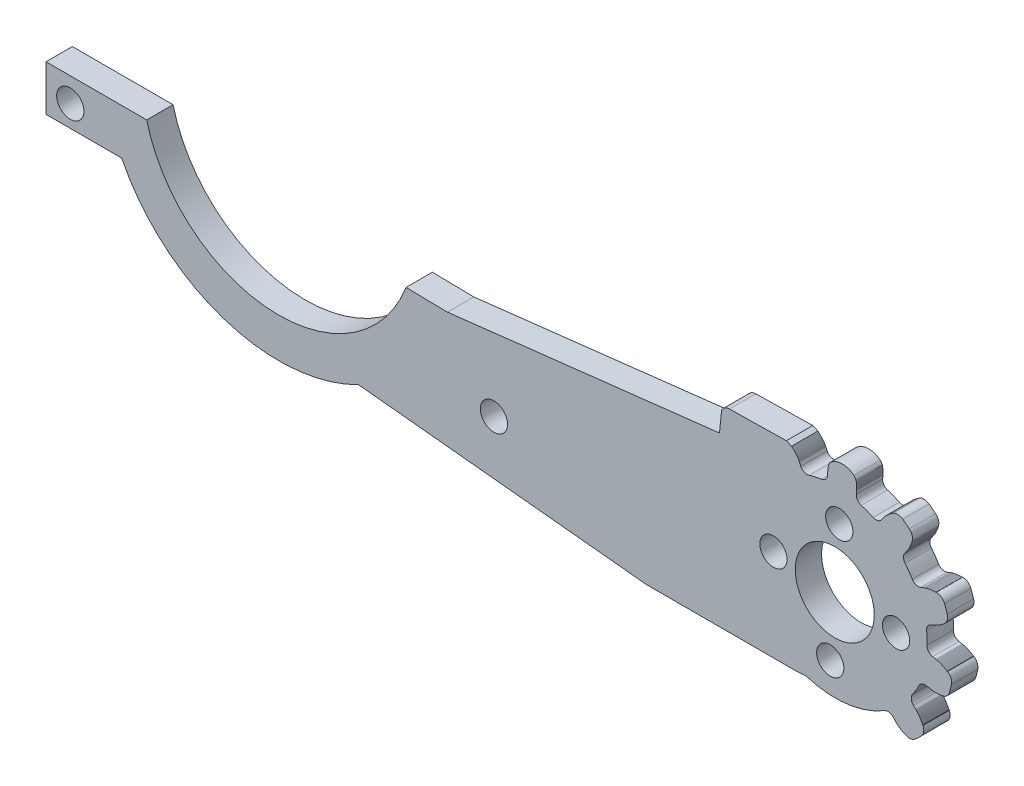
SolidWorks part; units mm, degrees
ref_plane "前视基准面" through (0, 0, 0) normal (0, 0, 1) x (1, 0, 0)
ref_plane "上视基准面" through (0, 0, 0) normal (0, 1, 0) x (1, 0, 0)
ref_plane "右视基准面" through (0, 0, 0) normal (1, 0, 0) x (0, 0, -1)
sketch "Model" plane through (0, 0, 0) normal (0, 0, 1) x (1, 0, 0)
  line L0 (3139.6381, 1742.7841) -> (3139.6125, 1742.8095)
  line L1 (3139.6635, 1742.7586) -> (3139.6381, 1742.7841)
  line L2 (3139.8365, 1742.5753) -> (3139.8124, 1742.602)
  line L3 (3153.0408, 1740.3213) -> (3153.0525, 1740.3554)
  line L4 (3153.0289, 1740.2873) -> (3153.0408, 1740.3213)
  line L5 (3153.0169, 1740.2533) -> (3153.0289, 1740.2873)
  line L6 (3153.0046, 1740.2194) -> (3153.0169, 1740.2533)
  line L7 (3152.9921, 1740.1856) -> (3153.0046, 1740.2194)
  line L8 (3152.9795, 1740.1519) -> (3152.9921, 1740.1856)
  line L9 (3152.87, 1739.8856) -> (3152.8846, 1739.9185)
  line L10 (3152.8242, 1739.788) -> (3152.8398, 1739.8203)
  line L11 (3154.7478, 1736.7119) -> (3154.7132, 1736.7018)
  line L12 (3154.7825, 1736.7216) -> (3154.7478, 1736.7119)
  line L13 (3154.8172, 1736.7308) -> (3154.7825, 1736.7216)
  line L14 (3154.8521, 1736.7395) -> (3154.8172, 1736.7308)
  line L15 (3154.8871, 1736.7479) -> (3154.8521, 1736.7395)
  line L16 (3154.9222, 1736.7557) -> (3154.8871, 1736.7479)
  line L17 (3154.9574, 1736.7631) -> (3154.9222, 1736.7557)
  line L18 (3154.9926, 1736.77) -> (3154.9574, 1736.7631)
  line L19 (3155.028, 1736.7765) -> (3154.9926, 1736.77)
  line L20 (3155.0634, 1736.7826) -> (3155.028, 1736.7765)
  line L21 (3155.1344, 1736.7936) -> (3155.0989, 1736.7883)
  line L22 (3155.17, 1736.7985) -> (3155.1344, 1736.7936)
  line L23 (3156.468, 1733.9968) -> (3156.497, 1734.0182)
  line L24 (3156.4389, 1733.9757) -> (3156.468, 1733.9968)
  line L25 (3156.4096, 1733.9547) -> (3156.4389, 1733.9757)
  line L26 (3156.3802, 1733.9339) -> (3156.4096, 1733.9547)
  line L27 (3156.3506, 1733.9134) -> (3156.3802, 1733.9339)
  line L28 (3156.3209, 1733.8931) -> (3156.3506, 1733.9134)
  line L29 (3156.291, 1733.8731) -> (3156.3209, 1733.8931)
  line L30 (3156.2609, 1733.8533) -> (3156.291, 1733.8731)
  line L31 (3156.2307, 1733.8339) -> (3156.2609, 1733.8533)
  line L32 (3156.2003, 1733.8148) -> (3156.2307, 1733.8339)
  line L33 (3156.1696, 1733.796) -> (3156.2003, 1733.8148)
  line L34 (3156.4614, 1730.0427) -> (3156.4285, 1730.0571)
  line L35 (3156.4942, 1730.028) -> (3156.4614, 1730.0427)
  line L36 (3156.5269, 1730.0129) -> (3156.4942, 1730.028)
  line L37 (3155.2801, 1726.9965) -> (3155.3155, 1726.99)
  line L38 (3155.2448, 1727.0034) -> (3155.2801, 1726.9965)
  line L39 (3155.1394, 1727.0265) -> (3155.1744, 1727.0185)
  line L40 (3155.1044, 1727.035) -> (3155.1394, 1727.0265)
  line L41 (3154.7261, 1727.0734) -> (3155.1044, 1727.035)
  line L42 (3139.9527, 1742.4382) -> (3139.9301, 1742.4661)
  line L43 (3139.9751, 1742.4101) -> (3139.9527, 1742.4382)
  line L44 (3152.9666, 1740.1183) -> (3152.9795, 1740.1519)
  line L45 (3152.9267, 1740.0179) -> (3152.9402, 1740.0512)
  line L46 (3152.8989, 1739.9515) -> (3152.9129, 1739.9846)
  line L47 (3152.8846, 1739.9185) -> (3152.8989, 1739.9515)
  line L48 (3155.3488, 1736.8185) -> (3155.313, 1736.8151)
  line L49 (3152.8551, 1739.8529) -> (3152.87, 1739.8856)
  line L50 (3152.8398, 1739.8203) -> (3152.8551, 1739.8529)
  line L51 (3152.8082, 1739.7558) -> (3152.8242, 1739.788)
  line L52 (3152.7919, 1739.7238) -> (3152.8082, 1739.7558)
  line L53 (3155.2095, 1727.0108) -> (3155.2448, 1727.0034)
  line L54 (3155.951, 1730.2151) -> (3155.916, 1730.2232)
  line L55 (3139.8603, 1742.5483) -> (3139.8365, 1742.5753)
  line L56 (3139.8838, 1742.5212) -> (3139.8603, 1742.5483)
  line L57 (3139.9071, 1742.4938) -> (3139.8838, 1742.5212)
  line L58 (3139.9301, 1742.4661) -> (3139.9071, 1742.4938)
  line L59 (3139.997, 1742.3817) -> (3139.9751, 1742.4101)
  line L60 (3152.9535, 1740.0847) -> (3152.9666, 1740.1183)
  line L61 (3152.9402, 1740.0512) -> (3152.9535, 1740.0847)
  line L62 (3140.0607, 1742.2947) -> (3140.0399, 1742.324)
  line L63 (3155.2057, 1736.8031) -> (3155.17, 1736.7985)
  line L64 (3152.9129, 1739.9846) -> (3152.9267, 1740.0179)
  line L65 (3156.497, 1734.0182) -> (3156.5259, 1734.0397)
  line L66 (3154.179, 1723.2587) -> (3154.162, 1723.2905)
  line L67 (3154.1959, 1723.2269) -> (3154.179, 1723.2587)
  line L68 (3154.2125, 1723.1949) -> (3154.1959, 1723.2269)
  line L69 (3154.2289, 1723.1628) -> (3154.2125, 1723.1949)
  line L70 (3154.2452, 1723.1307) -> (3154.2289, 1723.1628)
  line L71 (3154.2612, 1723.0984) -> (3154.2452, 1723.1307)
  line L72 (3154.277, 1723.066) -> (3154.2612, 1723.0984)
  line L73 (3154.2927, 1723.0336) -> (3154.277, 1723.066)
  line L74 (3154.3081, 1723.001) -> (3154.2927, 1723.0336)
  line L75 (3154.3338, 1722.9732) -> (3154.3081, 1723.001)
  line L76 (3152.3422, 1721.044) -> (3152.3796, 1721.0389)
  line L77 (3152.3097, 1721.0596) -> (3152.3422, 1721.044)
  line L78 (3152.2773, 1721.0754) -> (3152.3097, 1721.0596)
  line L79 (3155.0989, 1736.7883) -> (3155.0634, 1736.7826)
  line L80 (3140.0399, 1742.324) -> (3140.0186, 1742.353)
  line L81 (3156.0903, 1730.1784) -> (3156.0556, 1730.1882)
  line L82 (3156.1248, 1730.1682) -> (3156.0903, 1730.1784)
  line L83 (3152.2451, 1721.0914) -> (3152.2773, 1721.0754)
  line L84 (3152.2129, 1721.1075) -> (3152.2451, 1721.0914)
  line L85 (3156.4285, 1730.0571) -> (3156.3954, 1730.0711)
  line L86 (3146.7836, 1742.877) -> (3146.781, 1742.9128)
  line L87 (3146.7858, 1742.8411) -> (3146.7836, 1742.877)
  line L88 (3146.7875, 1742.8052) -> (3146.7858, 1742.8411)
  line L89 (3146.7888, 1742.7692) -> (3146.7875, 1742.8052)
  line L90 (3146.7896, 1742.7333) -> (3146.7888, 1742.7692)
  line L91 (3146.7899, 1742.6973) -> (3146.7896, 1742.7333)
  line L92 (3146.7898, 1742.6613) -> (3146.7899, 1742.6973)
  line L93 (3146.7893, 1742.6253) -> (3146.7898, 1742.6613)
  line L94 (3146.7883, 1742.5893) -> (3146.7893, 1742.6253)
  line L95 (3146.7869, 1742.5533) -> (3146.7883, 1742.5893)
  line L96 (3146.7851, 1742.5174) -> (3146.7869, 1742.5533)
  line L97 (3146.7828, 1742.4815) -> (3146.7851, 1742.5174)
  line L98 (3146.7802, 1742.4456) -> (3146.7828, 1742.4815)
  line L99 (3146.7772, 1742.4097) -> (3146.7802, 1742.4456)
  line L100 (3146.7738, 1742.374) -> (3146.7772, 1742.4097)
  line L101 (3146.7513, 1741.9979) -> (3146.7738, 1742.374)
  line L102 (3149.8509, 1741.2183) -> (3149.6326, 1740.9116)
  line L103 (3140.0186, 1742.353) -> (3139.997, 1742.3817)
  line L104 (3149.8719, 1741.2475) -> (3149.8509, 1741.2183)
  line L105 (3149.8932, 1741.2765) -> (3149.8719, 1741.2475)
  line L106 (3149.9149, 1741.3052) -> (3149.8932, 1741.2765)
  line L107 (3155.2414, 1736.8074) -> (3155.2057, 1736.8031)
  line L108 (3155.2772, 1736.8114) -> (3155.2414, 1736.8074)
  line L109 (3155.313, 1736.8151) -> (3155.2772, 1736.8114)
  line L110 (3156.4629, 1726.9866) -> (3156.4986, 1726.9911)
  line L111 (3156.4271, 1726.9824) -> (3156.4629, 1726.9866)
  line L112 (3155.986, 1730.2065) -> (3155.951, 1730.2151)
  line L113 (3156.0209, 1730.1976) -> (3155.986, 1730.2065)
  line L114 (3156.0556, 1730.1882) -> (3156.0209, 1730.1976)
  line L115 (3156.1592, 1730.1576) -> (3156.1248, 1730.1682)
  line L116 (3156.7523, 1734.2181) -> (3156.7799, 1734.2412)
  line L117 (3156.7245, 1734.1952) -> (3156.7523, 1734.2181)
  line L118 (3156.6965, 1734.1725) -> (3156.7245, 1734.1952)
  line L119 (3156.6684, 1734.1499) -> (3156.6965, 1734.1725)
  line L120 (3156.6402, 1734.1275) -> (3156.6684, 1734.1499)
  line L121 (3156.6118, 1734.1053) -> (3156.6402, 1734.1275)
  line L122 (3156.5833, 1734.0833) -> (3156.6118, 1734.1053)
  line L123 (3156.5547, 1734.0614) -> (3156.5833, 1734.0833)
  line L124 (3156.5259, 1734.0397) -> (3156.5547, 1734.0614)
  line L125 (3153.0639, 1740.3896) -> (3153.0751, 1740.4238)
  line L126 (3153.0525, 1740.3554) -> (3153.0639, 1740.3896)
  line L127 (3155.2459, 1733.3476) -> (3155.5833, 1733.5244)
  line L128 (3156.1934, 1730.1466) -> (3156.1592, 1730.1576)
  line L129 (3156.2275, 1730.1351) -> (3156.1934, 1730.1466)
  line L130 (3156.2615, 1730.1232) -> (3156.2275, 1730.1351)
  line L131 (3156.2952, 1730.1108) -> (3156.2615, 1730.1232)
  line L132 (3156.3288, 1730.098) -> (3156.2952, 1730.1108)
  line L133 (3156.3622, 1730.0848) -> (3156.3288, 1730.098)
  line L134 (3156.3954, 1730.0711) -> (3156.3622, 1730.0848)
  line L135 (3143.5454, 1743.0444) -> (3143.5389, 1743.0091)
  line L136 (3143.5524, 1743.0797) -> (3143.5454, 1743.0444)
  line L137 (3143.5598, 1743.1149) -> (3143.5524, 1743.0797)
  line L138 (3143.5677, 1743.15) -> (3143.5598, 1743.1149)
  line L139 (3143.5761, 1743.1849) -> (3143.5677, 1743.15)
  line L140 (3143.5848, 1743.2197) -> (3143.5761, 1743.1849)
  line L141 (3143.594, 1743.2545) -> (3143.5848, 1743.2197)
  line L142 (3143.6036, 1743.2891) -> (3143.594, 1743.2545)
  line L143 (3143.6135, 1743.3237) -> (3143.6036, 1743.2891)
  line L144 (3143.6345, 1743.3925) -> (3143.6238, 1743.3581)
  line L145 (3143.6454, 1743.4267) -> (3143.6345, 1743.3925)
  line L146 (3143.6567, 1743.4609) -> (3143.6454, 1743.4267)
  line L147 (3143.6682, 1743.495) -> (3143.6567, 1743.4609)
  line L148 (3143.68, 1743.5291) -> (3143.6682, 1743.495)
  line L149 (3143.686, 1743.546) -> (3143.68, 1743.5291)
  line L150 (3156.1388, 1733.7775) -> (3156.1696, 1733.796)
  line L151 (3156.1077, 1733.7594) -> (3156.1388, 1733.7775)
  line L152 (3155.5833, 1733.5244) -> (3155.6173, 1733.5362)
  line L153 (3155.8104, 1730.2453) -> (3155.4407, 1730.3164)
  line L154 (3155.8457, 1730.2383) -> (3155.8104, 1730.2453)
  line L155 (3155.8809, 1730.231) -> (3155.8457, 1730.2383)
  line L156 (3155.916, 1730.2232) -> (3155.8809, 1730.231)
  line L157 (3146.7256, 1743.3043) -> (3146.7187, 1743.3396)
  line L158 (3146.7323, 1743.2689) -> (3146.7256, 1743.3043)
  line L159 (3146.7387, 1743.2335) -> (3146.7323, 1743.2689)
  line L160 (3146.7448, 1743.198) -> (3146.7387, 1743.2335)
  line L161 (3146.7506, 1743.1625) -> (3146.7448, 1743.198)
  line L162 (3146.7561, 1743.127) -> (3146.7506, 1743.1625)
  line L163 (3146.7612, 1743.0914) -> (3146.7561, 1743.127)
  line L164 (3146.7659, 1743.0557) -> (3146.7612, 1743.0914)
  line L165 (3146.7703, 1743.0201) -> (3146.7659, 1743.0557)
  line L166 (3146.7743, 1742.9844) -> (3146.7703, 1743.0201)
  line L167 (3146.7779, 1742.9486) -> (3146.7743, 1742.9844)
  line L168 (3146.781, 1742.9128) -> (3146.7779, 1742.9486)
  line L169 (3153.0969, 1740.4925) -> (3153.0997, 1740.5293)
  line L170 (3156.0765, 1733.7417) -> (3156.1077, 1733.7594)
  line L171 (3155.7852, 1733.6007) -> (3155.8184, 1733.6147)
  line L172 (3155.7519, 1733.587) -> (3155.7852, 1733.6007)
  line L173 (3155.7185, 1733.5737) -> (3155.7519, 1733.587)
  line L174 (3155.6849, 1733.5608) -> (3155.7185, 1733.5737)
  line L175 (3155.6512, 1733.5483) -> (3155.6849, 1733.5608)
  line L176 (3155.6173, 1733.5362) -> (3155.6512, 1733.5483)
  line L177 (3151.8657, 1721.2984) -> (3151.8967, 1721.28)
  line L178 (3152.7752, 1739.692) -> (3152.7919, 1739.7238)
  line L179 (3152.7225, 1739.5979) -> (3152.7405, 1739.629)
  line L180 (3139.5087, 1742.9095) -> (3139.4824, 1742.9341)
  line L181 (3139.5349, 1742.8847) -> (3139.5087, 1742.9095)
  line L182 (3139.5609, 1742.8598) -> (3139.5349, 1742.8847)
  line L183 (3139.5868, 1742.8347) -> (3139.5609, 1742.8598)
  line L184 (3139.6125, 1742.8095) -> (3139.5868, 1742.8347)
  line L185 (3154.5424, 1736.6452) -> (3154.5087, 1736.6328)
  line L186 (3139.6888, 1742.7329) -> (3139.6635, 1742.7586)
  line L187 (3139.7139, 1742.707) -> (3139.6888, 1742.7329)
  line L188 (3139.7388, 1742.6811) -> (3139.7139, 1742.707)
  line L189 (3139.7635, 1742.6549) -> (3139.7388, 1742.6811)
  line L190 (3139.7881, 1742.6285) -> (3139.7635, 1742.6549)
  line L191 (3139.8124, 1742.602) -> (3139.7881, 1742.6285)
  line L192 (3140.0812, 1742.2651) -> (3140.0607, 1742.2947)
  line L193 (3140.1013, 1742.2353) -> (3140.0812, 1742.2651)
  line L194 (3140.1211, 1742.2052) -> (3140.1013, 1742.2353)
  line L195 (3140.1404, 1742.1748) -> (3140.1211, 1742.2052)
  line L196 (3140.1594, 1742.1443) -> (3140.1404, 1742.1748)
  line L197 (3140.1781, 1742.1135) -> (3140.1594, 1742.1443)
  line L198 (3140.1963, 1742.0824) -> (3140.1781, 1742.1135)
  line L199 (3140.2143, 1742.0512) -> (3140.1963, 1742.0824)
  line L200 (3140.2318, 1742.0198) -> (3140.2143, 1742.0512)
  line L201 (3140.249, 1741.9882) -> (3140.2318, 1742.0198)
  line L202 (3140.2658, 1741.9564) -> (3140.249, 1741.9882)
  line L203 (3140.2823, 1741.9245) -> (3140.2658, 1741.9564)
  line L204 (3140.4359, 1741.5802) -> (3140.2823, 1741.9245)
  line L205 (3143.4957, 1742.6159) -> (3143.4779, 1742.2399)
  line L206 (3143.4976, 1742.6518) -> (3143.4957, 1742.6159)
  line L207 (3143.4999, 1742.6877) -> (3143.4976, 1742.6518)
  line L208 (3143.5026, 1742.7235) -> (3143.4999, 1742.6877)
  line L209 (3143.5056, 1742.7594) -> (3143.5026, 1742.7235)
  line L210 (3143.5091, 1742.7952) -> (3143.5056, 1742.7594)
  line L211 (3143.513, 1742.831) -> (3143.5091, 1742.7952)
  line L212 (3143.5173, 1742.8668) -> (3143.513, 1742.831)
  line L213 (3143.5221, 1742.9024) -> (3143.5173, 1742.8668)
  line L214 (3143.5272, 1742.9381) -> (3143.5221, 1742.9024)
  line L215 (3143.5329, 1742.9736) -> (3143.5272, 1742.9381)
  line L216 (3143.5389, 1743.0091) -> (3143.5329, 1742.9736)
  line L217 (3154.0741, 1723.4476) -> (3154.0559, 1723.4787)
  line L218 (3154.0921, 1723.4164) -> (3154.0741, 1723.4476)
  line L219 (3154.1099, 1723.3851) -> (3154.0921, 1723.4164)
  line L220 (3154.1274, 1723.3537) -> (3154.1099, 1723.3851)
  line L221 (3154.1448, 1723.3221) -> (3154.1274, 1723.3537)
  line L222 (3154.162, 1723.2905) -> (3154.1448, 1723.3221)
  line L223 (3150.8201, 1742.1198) -> (3150.7904, 1742.0996)
  line L224 (3150.85, 1742.1399) -> (3150.8201, 1742.1198)
  line L225 (3150.8801, 1742.1598) -> (3150.85, 1742.1399)
  line L226 (3150.9061, 1742.1859) -> (3150.8801, 1742.1598)
  line L227 (3153.0861, 1740.4581) -> (3153.0969, 1740.4925)
  line L228 (3153.0751, 1740.4238) -> (3153.0861, 1740.4581)
  line L229 (3156.045, 1733.7244) -> (3156.0765, 1733.7417)
  line L230 (3156.0133, 1733.7075) -> (3156.045, 1733.7244)
  line L231 (3155.9491, 1733.675) -> (3155.9813, 1733.691)
  line L232 (3155.9167, 1733.6593) -> (3155.9491, 1733.675)
  line L233 (3155.8841, 1733.644) -> (3155.9167, 1733.6593)
  line L234 (3155.8513, 1733.6292) -> (3155.8841, 1733.644)
  line L235 (3155.8184, 1733.6147) -> (3155.8513, 1733.6292)
  line L236 (3152.0851, 1721.1742) -> (3152.1169, 1721.1573)
  line L237 (3152.0534, 1721.1914) -> (3152.0851, 1721.1742)
  line L238 (3152.0218, 1721.2087) -> (3152.0534, 1721.1914)
  line L239 (3151.9904, 1721.2263) -> (3152.0218, 1721.2087)
  line L240 (3151.959, 1721.244) -> (3151.9904, 1721.2263)
  line L241 (3151.9278, 1721.2619) -> (3151.959, 1721.244)
  line L242 (3151.8967, 1721.28) -> (3151.9278, 1721.2619)
  line L243 (3150.0998, 1741.5257) -> (3150.0755, 1741.4992)
  line L244 (3151.7135, 1721.3942) -> (3151.7436, 1721.3744)
  line L245 (3151.6837, 1721.4142) -> (3151.7135, 1721.3942)
  line L246 (3151.6247, 1721.4553) -> (3151.6541, 1721.4346)
  line L247 (3151.5956, 1721.4764) -> (3151.6247, 1721.4553)
  line L248 (3151.5668, 1721.4979) -> (3151.5956, 1721.4764)
  line L249 (3151.5383, 1721.5197) -> (3151.5668, 1721.4979)
  line L250 (3151.51, 1721.5419) -> (3151.5383, 1721.5197)
  line L251 (3151.482, 1721.5645) -> (3151.51, 1721.5419)
  line L252 (3151.4543, 1721.5875) -> (3151.482, 1721.5645)
  line L253 (3151.4269, 1721.6108) -> (3151.4543, 1721.5875)
  line L254 (3151.3998, 1721.6345) -> (3151.4269, 1721.6108)
  line L255 (3151.3729, 1721.6584) -> (3151.3998, 1721.6345)
  line L256 (3151.3464, 1721.6827) -> (3151.3729, 1721.6584)
  line L257 (3151.3201, 1721.7074) -> (3151.3464, 1721.6827)
  line L258 (3151.2941, 1721.7323) -> (3151.3201, 1721.7074)
  line L259 (3151.2684, 1721.7575) -> (3151.2941, 1721.7323)
  line L260 (3151.243, 1721.783) -> (3151.2684, 1721.7575)
  line L261 (3151.2179, 1721.8087) -> (3151.243, 1721.783)
  line L262 (3151.1931, 1721.8347) -> (3151.2179, 1721.8087)
  line L263 (3150.9347, 1722.1084) -> (3151.1931, 1721.8347)
  line L264 (3155.1744, 1727.0185) -> (3155.2095, 1727.0108)
  line L265 (3156.8465, 1729.8473) -> (3156.815, 1729.8648)
  line L266 (3156.8779, 1729.8296) -> (3156.8465, 1729.8473)
  line L267 (3149.9368, 1741.3337) -> (3149.9149, 1741.3052)
  line L268 (3149.9591, 1741.3619) -> (3149.9368, 1741.3337)
  line L269 (3149.9818, 1741.3899) -> (3149.9591, 1741.3619)
  line L270 (3150.0047, 1741.4177) -> (3149.9818, 1741.3899)
  line L271 (3150.028, 1741.4451) -> (3150.0047, 1741.4177)
  line L272 (3150.0516, 1741.4723) -> (3150.028, 1741.4451)
  line L273 (3150.0755, 1741.4992) -> (3150.0516, 1741.4723)
  line L274 (3155.4565, 1736.8273) -> (3155.4206, 1736.8246)
  line L275 (3150.1244, 1741.552) -> (3150.0998, 1741.5257)
  line L276 (3150.1493, 1741.5779) -> (3150.1244, 1741.552)
  line L277 (3150.1746, 1741.6034) -> (3150.1493, 1741.5779)
  line L278 (3150.2002, 1741.6287) -> (3150.1746, 1741.6034)
  line L279 (3150.2261, 1741.6536) -> (3150.2002, 1741.6287)
  line L280 (3150.2523, 1741.6781) -> (3150.2261, 1741.6536)
  line L281 (3150.2788, 1741.7024) -> (3150.2523, 1741.6781)
  line L282 (3150.3056, 1741.7264) -> (3150.2788, 1741.7024)
  line L283 (3150.3327, 1741.7501) -> (3150.3056, 1741.7264)
  line L284 (3150.36, 1741.7735) -> (3150.3327, 1741.7501)
  line L285 (3150.3875, 1741.7966) -> (3150.36, 1741.7735)
  line L286 (3150.4152, 1741.8195) -> (3150.3875, 1741.7966)
  line L287 (3150.4432, 1741.8422) -> (3150.4152, 1741.8195)
  line L288 (3150.4713, 1741.8647) -> (3150.4432, 1741.8422)
  line L289 (3150.4996, 1741.8869) -> (3150.4713, 1741.8647)
  line L290 (3150.5281, 1741.909) -> (3150.4996, 1741.8869)
  line L291 (3150.5567, 1741.9308) -> (3150.5281, 1741.909)
  line L292 (3150.5854, 1741.9525) -> (3150.5567, 1741.9308)
  line L293 (3150.6143, 1741.9741) -> (3150.5854, 1741.9525)
  line L294 (3150.6433, 1741.9954) -> (3150.6143, 1741.9741)
  line L295 (3150.6725, 1742.0166) -> (3150.6433, 1741.9954)
  line L296 (3150.7018, 1742.0376) -> (3150.6725, 1742.0166)
  line L297 (3150.7312, 1742.0584) -> (3150.7018, 1742.0376)
  line L298 (3150.7607, 1742.0791) -> (3150.7312, 1742.0584)
  line L299 (3150.7904, 1742.0996) -> (3150.7607, 1742.0791)
  line L300 (3155.3865, 1726.9783) -> (3155.4221, 1726.973)
  line L301 (3155.351, 1726.9839) -> (3155.3865, 1726.9783)
  line L302 (3155.3155, 1726.99) -> (3155.351, 1726.9839)
  line L303 (3154.6103, 1736.6691) -> (3154.5763, 1736.6573)
  line L304 (3154.6445, 1736.6804) -> (3154.6103, 1736.6691)
  line L305 (3154.6788, 1736.6913) -> (3154.6445, 1736.6804)
  line L306 (3154.7132, 1736.7018) -> (3154.6788, 1736.6913)
  line L307 (3156.7517, 1729.8993) -> (3156.7199, 1729.9162)
  line L308 (3156.7834, 1729.8821) -> (3156.7517, 1729.8993)
  line L309 (3156.815, 1729.8648) -> (3156.7834, 1729.8821)
  line L310 (3152.6853, 1739.5363) -> (3152.7041, 1739.5669)
  line L311 (3152.6662, 1739.5058) -> (3152.6853, 1739.5363)
  line L312 (3156.9091, 1729.8117) -> (3156.8779, 1729.8296)
  line L313 (3156.9403, 1729.7936) -> (3156.9091, 1729.8117)
  line L314 (3156.9713, 1729.7753) -> (3156.9403, 1729.7936)
  line L315 (3155.9813, 1733.691) -> (3156.0133, 1733.7075)
  line L316 (3157.0331, 1729.7381) -> (3157.0023, 1729.7568)
  line L317 (3157.0638, 1729.7193) -> (3157.0331, 1729.7381)
  line L318 (3152.1808, 1721.1239) -> (3152.2129, 1721.1075)
  line L319 (3152.1488, 1721.1405) -> (3152.1808, 1721.1239)
  line L320 (3152.1169, 1721.1573) -> (3152.1488, 1721.1405)
  line L321 (3153.5226, 1724.1537) -> (3153.2501, 1724.4134)
  line L322 (3153.5485, 1724.1288) -> (3153.5226, 1724.1537)
  line L323 (3155.3847, 1736.8216) -> (3155.3488, 1736.8185)
  line L324 (3155.4206, 1736.8246) -> (3155.3847, 1736.8216)
  line L325 (3156.3913, 1726.9784) -> (3156.4271, 1726.9824)
  line L326 (3155.4925, 1736.8298) -> (3155.4565, 1736.8273)
  line L327 (3151.8349, 1721.317) -> (3151.8657, 1721.2984)
  line L328 (3151.8043, 1721.3359) -> (3151.8349, 1721.317)
  line L329 (3152.758, 1739.6604) -> (3152.7752, 1739.692)
  line L330 (3152.7405, 1739.629) -> (3152.758, 1739.6604)
  line L331 (3155.7084, 1736.8402) -> (3155.6724, 1736.839)
  line L332 (3152.7041, 1739.5669) -> (3152.7225, 1739.5979)
  line L333 (3155.7444, 1736.8411) -> (3155.7084, 1736.8402)
  line L334 (3155.7804, 1736.8419) -> (3155.7444, 1736.8411)
  line L335 (3152.6466, 1739.4756) -> (3152.6662, 1739.5058)
  line L336 (3152.6267, 1739.4456) -> (3152.6466, 1739.4756)
  line L337 (3152.6064, 1739.4159) -> (3152.6267, 1739.4456)
  line L338 (3152.5858, 1739.3864) -> (3152.6064, 1739.4159)
  line L339 (3152.5648, 1739.3571) -> (3152.5858, 1739.3864)
  line L340 (3152.5435, 1739.3281) -> (3152.5648, 1739.3571)
  line L341 (3152.5219, 1739.2993) -> (3152.5435, 1739.3281)
  line L342 (3152.5, 1739.2708) -> (3152.5219, 1739.2993)
  line L343 (3152.4778, 1739.2425) -> (3152.5, 1739.2708)
  line L344 (3152.2785, 1738.9201) -> (3152.4778, 1739.2425)
  line L345 (3154.4416, 1736.6067) -> (3154.0922, 1736.4667)
  line L346 (3154.4751, 1736.6199) -> (3154.4416, 1736.6067)
  line L347 (3154.5087, 1736.6328) -> (3154.4751, 1736.6199)
  line L348 (3156.5593, 1729.9974) -> (3156.5269, 1730.0129)
  line L349 (3154.5763, 1736.6573) -> (3154.5424, 1736.6452)
  line L350 (3156.5917, 1729.9817) -> (3156.5593, 1729.9974)
  line L351 (3156.6239, 1729.9657) -> (3156.5917, 1729.9817)
  line L352 (3156.6561, 1729.9495) -> (3156.6239, 1729.9657)
  line L353 (3156.6881, 1729.933) -> (3156.6561, 1729.9495)
  line L354 (3156.7199, 1729.9162) -> (3156.6881, 1729.933)
  line L355 (3156.14, 1726.9564) -> (3156.176, 1726.9589)
  line L356 (3153.7455, 1723.9189) -> (3153.7219, 1723.9461)
  line L357 (3156.1041, 1726.9542) -> (3156.14, 1726.9564)
  line L358 (3155.8165, 1736.8424) -> (3155.7804, 1736.8419)
  line L359 (3155.8524, 1736.8561) -> (3155.8165, 1736.8424)
  line L360 (3153.9206, 1723.6909) -> (3153.9, 1723.7203)
  line L361 (3157.0023, 1729.7568) -> (3156.9713, 1729.7753)
  line L362 (3156.7799, 1734.2412) -> (3156.7986, 1734.2749)
  line L363 (3157.0944, 1729.7002) -> (3157.0638, 1729.7193)
  line L364 (3157.1328, 1729.6935) -> (3157.0944, 1729.7002)
  line L365 (3156.4986, 1726.9911) -> (3156.5323, 1727.0105)
  line L366 (3153.5741, 1724.1035) -> (3153.5485, 1724.1288)
  line L367 (3156.3554, 1726.9746) -> (3156.3913, 1726.9784)
  line L368 (3155.5284, 1736.8321) -> (3155.4925, 1736.8298)
  line L369 (3155.5644, 1736.8341) -> (3155.5284, 1736.8321)
  line L370 (3155.6004, 1736.836) -> (3155.5644, 1736.8341)
  line L371 (3155.6364, 1736.8376) -> (3155.6004, 1736.836)
  line L372 (3155.6724, 1736.839) -> (3155.6364, 1736.8376)
  line L373 (3151.7436, 1721.3744) -> (3151.7738, 1721.355)
  line L374 (3156.176, 1726.9589) -> (3156.2119, 1726.9616)
  line L375 (3151.6541, 1721.4346) -> (3151.6837, 1721.4142)
  line L376 (3156.0321, 1726.9503) -> (3156.0681, 1726.9521)
  line L377 (3153.9409, 1723.6612) -> (3153.9206, 1723.6909)
  line L378 (3154.0187, 1723.5403) -> (3153.9997, 1723.5708)
  line L379 (3154.0374, 1723.5096) -> (3154.0187, 1723.5403)
  line L380 (3154.0559, 1723.4787) -> (3154.0374, 1723.5096)
  line L381 (3155.6009, 1726.9537) -> (3155.6368, 1726.9512)
  line L382 (3155.5651, 1726.9566) -> (3155.6009, 1726.9537)
  line L383 (3155.5293, 1726.96) -> (3155.5651, 1726.9566)
  line L384 (3155.4935, 1726.9639) -> (3155.5293, 1726.96)
  line L385 (3155.4578, 1726.9683) -> (3155.4935, 1726.9639)
  line L386 (3155.4221, 1726.973) -> (3155.4578, 1726.9683)
  line L387 (3153.5995, 1724.078) -> (3153.5741, 1724.1035)
  line L388 (3156.3196, 1726.971) -> (3156.3554, 1726.9746)
  line L389 (3156.2837, 1726.9677) -> (3156.3196, 1726.971)
  line L390 (3156.2478, 1726.9645) -> (3156.2837, 1726.9677)
  line L391 (3151.7738, 1721.355) -> (3151.8043, 1721.3359)
  line L392 (3156.2119, 1726.9616) -> (3156.2478, 1726.9645)
  line L393 (3153.6981, 1723.9731) -> (3153.6739, 1723.9997)
  line L394 (3153.7219, 1723.9461) -> (3153.6981, 1723.9731)
  line L395 (3153.7686, 1723.8914) -> (3153.7455, 1723.9189)
  line L396 (3156.0681, 1726.9521) -> (3156.1041, 1726.9542)
  line L397 (3153.814, 1723.8355) -> (3153.7915, 1723.8636)
  line L398 (3155.9962, 1726.9487) -> (3156.0321, 1726.9503)
  line L399 (3155.9242, 1726.9465) -> (3155.9602, 1726.9475)
  line L400 (3155.8883, 1726.9458) -> (3155.9242, 1726.9465)
  line L401 (3138.7876, 1743.2782) -> (3132.2952, 1743.1634)
  line L402 (3139.3756, 1743.0308) -> (3138.7876, 1743.2782)
  line L403 (3139.4025, 1743.0069) -> (3139.3756, 1743.0308)
  line L404 (3139.4293, 1742.9828) -> (3139.4025, 1743.0069)
  line L405 (3153.8791, 1723.7495) -> (3153.8578, 1723.7785)
  line L406 (3153.6246, 1724.0522) -> (3153.5995, 1724.078)
  line L407 (3153.6494, 1724.0261) -> (3153.6246, 1724.0522)
  line L408 (3153.6739, 1723.9997) -> (3153.6494, 1724.0261)
  line L409 (3155.7085, 1726.9476) -> (3155.7445, 1726.9465)
  line L410 (3153.7915, 1723.8636) -> (3153.7686, 1723.8914)
  line L411 (3155.9602, 1726.9475) -> (3155.9962, 1726.9487)
  line L412 (3153.8578, 1723.7785) -> (3153.8361, 1723.8071)
  line L413 (3155.8523, 1726.9454) -> (3155.8883, 1726.9458)
  line L414 (3155.8163, 1726.9454) -> (3155.8523, 1726.9454)
  line L415 (3155.7804, 1726.9458) -> (3155.8163, 1726.9454)
  line L416 (3155.7445, 1726.9465) -> (3155.7804, 1726.9458)
  line L417 (3153.9804, 1723.6012) -> (3153.9608, 1723.6313)
  line L418 (3139.4559, 1742.9585) -> (3139.4293, 1742.9828)
  line L419 (3139.4824, 1742.9341) -> (3139.4559, 1742.9585)
  line L420 (3153.8361, 1723.8071) -> (3153.814, 1723.8355)
  line L421 (3155.6726, 1726.9492) -> (3155.7085, 1726.9476)
  line L422 (3153.9, 1723.7203) -> (3153.8791, 1723.7495)
  line L423 (3153.9608, 1723.6313) -> (3153.9409, 1723.6612)
  line L424 (3155.6368, 1726.9512) -> (3155.6726, 1726.9492)
  line L425 (3153.9997, 1723.5708) -> (3153.9804, 1723.6012)
  line L426 (3131.4116, 1742.5968) -> (3131.1697, 1740.2313)
  line L427 (3159.0065, 1766.84) -> (3159.0349, 1766.8694)
  line L428 (3158.978, 1766.8108) -> (3159.0065, 1766.84)
  line L429 (3158.9492, 1766.7818) -> (3158.978, 1766.8108)
  line L430 (3158.9203, 1766.7529) -> (3158.9492, 1766.7818)
  line L431 (3158.8912, 1766.7242) -> (3158.9203, 1766.7529)
  line L432 (3158.8619, 1766.6957) -> (3158.8912, 1766.7242)
  line L433 (3158.8325, 1766.6674) -> (3158.8619, 1766.6957)
  line L434 (3158.8028, 1766.6393) -> (3158.8325, 1766.6674)
  line L435 (3158.773, 1766.6114) -> (3158.8028, 1766.6393)
  line L436 (3158.743, 1766.5837) -> (3158.773, 1766.6114)
  line L437 (3158.7128, 1766.5561) -> (3158.743, 1766.5837)
  line L438 (3158.6824, 1766.5288) -> (3158.7128, 1766.5561)
  line L439 (3158.6519, 1766.5017) -> (3158.6824, 1766.5288)
  line L440 (3158.6211, 1766.4747) -> (3158.6519, 1766.5017)
  line L441 (3158.5902, 1766.448) -> (3158.6211, 1766.4747)
  line L442 (3158.5591, 1766.4215) -> (3158.5902, 1766.448)
  line L443 (3158.5278, 1766.3952) -> (3158.5591, 1766.4215)
  line L444 (3158.4963, 1766.369) -> (3158.5278, 1766.3952)
  line L445 (3158.4647, 1766.3431) -> (3158.4963, 1766.369)
  line L446 (3158.4328, 1766.3175) -> (3158.4647, 1766.3431)
  line L447 (3158.4007, 1766.2921) -> (3158.4328, 1766.3175)
  line L448 (3158.3685, 1766.2669) -> (3158.4007, 1766.2921)
  line L449 (3158.336, 1766.242) -> (3158.3685, 1766.2669)
  line L450 (3158.3033, 1766.2174) -> (3158.336, 1766.242)
  line L451 (3158.2704, 1766.1932) -> (3158.3033, 1766.2174)
  line L452 (3158.2372, 1766.1693) -> (3158.2704, 1766.1932)
  line L453 (3158.2038, 1766.1457) -> (3158.2372, 1766.1693)
  line L454 (3158.1701, 1766.1225) -> (3158.2038, 1766.1457)
  line L455 (3158.1362, 1766.0997) -> (3158.1701, 1766.1225)
  line L456 (3158.102, 1766.0773) -> (3158.1362, 1766.0997)
  line L457 (3158.0676, 1766.0553) -> (3158.102, 1766.0773)
  line L458 (3158.0329, 1766.0338) -> (3158.0676, 1766.0553)
  line L459 (3157.9979, 1766.0127) -> (3158.0329, 1766.0338)
  line L460 (3157.9626, 1765.9921) -> (3157.9979, 1766.0127)
  line L461 (3157.927, 1765.972) -> (3157.9626, 1765.9921)
  line L462 (3157.8911, 1765.9523) -> (3157.927, 1765.972)
  line L463 (3157.8549, 1765.9332) -> (3157.8911, 1765.9523)
  line L464 (3157.8185, 1765.9145) -> (3157.8549, 1765.9332)
  line L465 (3157.7819, 1765.8963) -> (3157.8185, 1765.9145)
  line L466 (3157.745, 1765.8786) -> (3157.7819, 1765.8963)
  line L467 (3157.7079, 1765.8613) -> (3157.745, 1765.8786)
  line L468 (3157.6706, 1765.8445) -> (3157.7079, 1765.8613)
  line L469 (3157.6331, 1765.8281) -> (3157.6706, 1765.8445)
  line L470 (3157.5954, 1765.8122) -> (3157.6331, 1765.8281)
  line L471 (3157.5575, 1765.7968) -> (3157.5954, 1765.8122)
  line L472 (3157.5195, 1765.7818) -> (3157.5575, 1765.7968)
  line L473 (3157.4813, 1765.7673) -> (3157.5195, 1765.7818)
  line L474 (3157.4429, 1765.7532) -> (3157.4813, 1765.7673)
  line L475 (3157.7178, 1762.7102) -> (3157.6777, 1762.7182)
  line L476 (3157.7578, 1762.7017) -> (3157.7178, 1762.7102)
  line L477 (3157.7977, 1762.6928) -> (3157.7578, 1762.7017)
  line L478 (3157.8375, 1762.6833) -> (3157.7977, 1762.6928)
  line L479 (3157.8772, 1762.6734) -> (3157.8375, 1762.6833)
  line L480 (3157.9168, 1762.663) -> (3157.8772, 1762.6734)
  line L481 (3157.9562, 1762.6522) -> (3157.9168, 1762.663)
  line L482 (3157.9955, 1762.6408) -> (3157.9562, 1762.6522)
  line L483 (3158.0347, 1762.629) -> (3157.9955, 1762.6408)
  line L484 (3158.0737, 1762.6166) -> (3158.0347, 1762.629)
  line L485 (3158.1125, 1762.6038) -> (3158.0737, 1762.6166)
  line L486 (3158.1512, 1762.5904) -> (3158.1125, 1762.6038)
  line L487 (3158.1897, 1762.5765) -> (3158.1512, 1762.5904)
  line L488 (3158.2279, 1762.5621) -> (3158.1897, 1762.5765)
  line L489 (3158.266, 1762.5472) -> (3158.2279, 1762.5621)
  line L490 (3158.3038, 1762.5317) -> (3158.266, 1762.5472)
  line L491 (3158.3414, 1762.5158) -> (3158.3038, 1762.5317)
  line L492 (3158.3789, 1762.4994) -> (3158.3414, 1762.5158)
  line L493 (3158.4161, 1762.4825) -> (3158.3789, 1762.4994)
  line L494 (3158.4531, 1762.4652) -> (3158.4161, 1762.4825)
  line L495 (3158.4899, 1762.4474) -> (3158.4531, 1762.4652)
  line L496 (3158.5266, 1762.4293) -> (3158.4899, 1762.4474)
  line L497 (3158.563, 1762.4107) -> (3158.5266, 1762.4293)
  line L498 (3158.5993, 1762.3918) -> (3158.563, 1762.4107)
  line L499 (3158.6354, 1762.3726) -> (3158.5993, 1762.3918)
  line L500 (3158.6713, 1762.353) -> (3158.6354, 1762.3726)
  line L501 (3158.707, 1762.3331) -> (3158.6713, 1762.353)
  line L502 (3158.7426, 1762.3129) -> (3158.707, 1762.3331)
  line L503 (3158.7781, 1762.2924) -> (3158.7426, 1762.3129)
  line L504 (3158.8133, 1762.2717) -> (3158.7781, 1762.2924)
  line L505 (3158.8485, 1762.2508) -> (3158.8133, 1762.2717)
  line L506 (3158.8834, 1762.2296) -> (3158.8485, 1762.2508)
  line L507 (3158.9182, 1762.2082) -> (3158.8834, 1762.2296)
  line L508 (3158.9529, 1762.1865) -> (3158.9182, 1762.2082)
  line L509 (3158.9874, 1762.1646) -> (3158.9529, 1762.1865)
  line L510 (3159.0218, 1762.1425) -> (3158.9874, 1762.1646)
  line L511 (3159.056, 1762.1202) -> (3159.0218, 1762.1425)
  line L512 (3159.0901, 1762.0976) -> (3159.056, 1762.1202)
  line L513 (3159.124, 1762.0748) -> (3159.0901, 1762.0976)
  line L514 (3159.1577, 1762.0518) -> (3159.124, 1762.0748)
  line L515 (3159.1914, 1762.0286) -> (3159.1577, 1762.0518)
  line L516 (3159.2248, 1762.0052) -> (3159.1914, 1762.0286)
  line L517 (3159.2581, 1761.9815) -> (3159.2248, 1762.0052)
  line L518 (3159.2913, 1761.9577) -> (3159.2581, 1761.9815)
  line L519 (3159.3243, 1761.9336) -> (3159.2913, 1761.9577)
  line L520 (3159.3572, 1761.9093) -> (3159.3243, 1761.9336)
  line L521 (3159.3899, 1761.8848) -> (3159.3572, 1761.9093)
  line L522 (3159.4225, 1761.8602) -> (3159.3899, 1761.8848)
  line L523 (3158.8956, 1759.5473) -> (3158.9354, 1759.5567)
  line L524 (3158.8558, 1759.5382) -> (3158.8956, 1759.5473)
  line L525 (3158.8159, 1759.5293) -> (3158.8558, 1759.5382)
  line L526 (3158.776, 1759.5207) -> (3158.8159, 1759.5293)
  line L527 (3158.736, 1759.5123) -> (3158.776, 1759.5207)
  line L528 (3158.696, 1759.5041) -> (3158.736, 1759.5123)
  line L529 (3158.6559, 1759.4963) -> (3158.696, 1759.5041)
  line L530 (3158.6157, 1759.4886) -> (3158.6559, 1759.4963)
  line L531 (3158.5756, 1759.4813) -> (3158.6157, 1759.4886)
  line L532 (3158.5353, 1759.4742) -> (3158.5756, 1759.4813)
  line L533 (3158.495, 1759.4673) -> (3158.5353, 1759.4742)
  line L534 (3158.4547, 1759.4608) -> (3158.495, 1759.4673)
  line L535 (3158.4143, 1759.4544) -> (3158.4547, 1759.4608)
  line L536 (3158.3739, 1759.4484) -> (3158.4143, 1759.4544)
  line L537 (3158.3335, 1759.4426) -> (3158.3739, 1759.4484)
  line L538 (3158.293, 1759.4371) -> (3158.3335, 1759.4426)
  line L539 (3158.2524, 1759.4319) -> (3158.293, 1759.4371)
  line L540 (3158.2118, 1759.427) -> (3158.2524, 1759.4319)
  line L541 (3158.1712, 1759.4223) -> (3158.2118, 1759.427)
  line L542 (3158.1305, 1759.4179) -> (3158.1712, 1759.4223)
  line L543 (3158.0898, 1759.4139) -> (3158.1305, 1759.4179)
  line L544 (3158.049, 1759.4102) -> (3158.0898, 1759.4139)
  line L545 (3158.0083, 1759.4068) -> (3158.049, 1759.4102)
  line L546 (3157.9675, 1759.4038) -> (3158.0083, 1759.4068)
  line L547 (3157.9266, 1759.4012) -> (3157.9675, 1759.4038)
  line L548 (3157.8858, 1759.399) -> (3157.9266, 1759.4012)
  line L549 (3157.845, 1759.3972) -> (3157.8858, 1759.399)
  line L550 (3157.8041, 1759.3959) -> (3157.845, 1759.3972)
  line L551 (3157.7632, 1759.3951) -> (3157.8041, 1759.3959)
  line L552 (3157.7224, 1759.3947) -> (3157.7632, 1759.3951)
  line L553 (3157.6815, 1759.3948) -> (3157.7224, 1759.3947)
  line L554 (3157.6406, 1759.3955) -> (3157.6815, 1759.3948)
  line L555 (3157.5998, 1759.3967) -> (3157.6406, 1759.3955)
  line L556 (3157.559, 1759.3984) -> (3157.5998, 1759.3967)
  line L557 (3157.5181, 1759.4008) -> (3157.559, 1759.3984)
  line L558 (3157.4773, 1759.4036) -> (3157.5181, 1759.4008)
  line L559 (3157.4366, 1759.4071) -> (3157.4773, 1759.4036)
  line L560 (3157.3959, 1759.411) -> (3157.4366, 1759.4071)
  line L561 (3157.3552, 1759.4155) -> (3157.3959, 1759.411)
  line L562 (3157.3146, 1759.4205) -> (3157.3552, 1759.4155)
  line L563 (3157.274, 1759.4261) -> (3157.3146, 1759.4205)
  line L564 (3157.2336, 1759.4321) -> (3157.274, 1759.4261)
  line L565 (3157.1126, 1759.4531) -> (3157.1529, 1759.4456)
  line L566 (3157.0725, 1759.4611) -> (3157.1126, 1759.4531)
  line L567 (3157.0325, 1759.4695) -> (3157.0725, 1759.4611)
  line L568 (3156.9926, 1759.4784) -> (3157.0325, 1759.4695)
  line L569 (3155.5787, 1756.7699) -> (3155.5494, 1756.7983)
  line L570 (3155.6078, 1756.7411) -> (3155.5787, 1756.7699)
  line L571 (3155.6365, 1756.712) -> (3155.6078, 1756.7411)
  line L572 (3155.6649, 1756.6826) -> (3155.6365, 1756.712)
  line L573 (3155.6929, 1756.6528) -> (3155.6649, 1756.6826)
  line L574 (3155.7206, 1756.6226) -> (3155.6929, 1756.6528)
  line L575 (3155.7479, 1756.5922) -> (3155.7206, 1756.6226)
  line L576 (3155.7749, 1756.5613) -> (3155.7479, 1756.5922)
  line L577 (3155.8014, 1756.5302) -> (3155.7749, 1756.5613)
  line L578 (3155.8275, 1756.4987) -> (3155.8014, 1756.5302)
  line L579 (3155.8533, 1756.4669) -> (3155.8275, 1756.4987)
  line L580 (3155.8786, 1756.4348) -> (3155.8533, 1756.4669)
  line L581 (3155.9034, 1756.4023) -> (3155.8786, 1756.4348)
  line L582 (3155.9278, 1756.3695) -> (3155.9034, 1756.4023)
  line L583 (3155.9518, 1756.3363) -> (3155.9278, 1756.3695)
  line L584 (3155.9752, 1756.3029) -> (3155.9518, 1756.3363)
  line L585 (3155.9983, 1756.2691) -> (3155.9752, 1756.3029)
  line L586 (3156.0209, 1756.2351) -> (3155.9983, 1756.2691)
  line L587 (3156.0431, 1756.2008) -> (3156.0209, 1756.2351)
  line L588 (3156.0648, 1756.1662) -> (3156.0431, 1756.2008)
  line L589 (3156.0862, 1756.1314) -> (3156.0648, 1756.1662)
  line L590 (3156.1072, 1756.0963) -> (3156.0862, 1756.1314)
  line L591 (3156.1279, 1756.061) -> (3156.1072, 1756.0963)
  line L592 (3156.1482, 1756.0255) -> (3156.1279, 1756.061)
  line L593 (3156.1681, 1755.9898) -> (3156.1482, 1756.0255)
  line L594 (3156.1878, 1755.9539) -> (3156.1681, 1755.9898)
  line L595 (3156.2071, 1755.9178) -> (3156.1878, 1755.9539)
  line L596 (3156.2261, 1755.8816) -> (3156.2071, 1755.9178)
  line L597 (3156.2448, 1755.8452) -> (3156.2261, 1755.8816)
  line L598 (3156.2633, 1755.8087) -> (3156.2448, 1755.8452)
  line L599 (3156.2815, 1755.7721) -> (3156.2633, 1755.8087)
  line L600 (3156.2995, 1755.7354) -> (3156.2815, 1755.7721)
  line L601 (3156.3172, 1755.6985) -> (3156.2995, 1755.7354)
  line L602 (3156.3346, 1755.6615) -> (3156.3172, 1755.6985)
  line L603 (3156.3518, 1755.6245) -> (3156.3346, 1755.6615)
  line L604 (3156.3688, 1755.5873) -> (3156.3518, 1755.6245)
  line L605 (3156.3855, 1755.55) -> (3156.3688, 1755.5873)
  line L606 (3156.402, 1755.5126) -> (3156.3855, 1755.55)
  line L607 (3156.4341, 1755.4375) -> (3156.4182, 1755.4751)
  line L608 (3156.4806, 1755.3241) -> (3156.4654, 1755.362)
  line L609 (3154.7064, 1753.5291) -> (3154.7446, 1753.5146)
  line L610 (3154.6683, 1753.5439) -> (3154.7064, 1753.5291)
  line L611 (3154.6303, 1753.559) -> (3154.6683, 1753.5439)
  line L612 (3154.5547, 1753.5898) -> (3154.5924, 1753.5742)
  line L613 (3154.517, 1753.6056) -> (3154.5547, 1753.5898)
  line L614 (3154.4794, 1753.6216) -> (3154.517, 1753.6056)
  line L615 (3154.4419, 1753.6378) -> (3154.4794, 1753.6216)
  line L616 (3154.4045, 1753.6544) -> (3154.4419, 1753.6378)
  line L617 (3154.3673, 1753.6711) -> (3154.4045, 1753.6544)
  line L618 (3154.3301, 1753.6882) -> (3154.3673, 1753.6711)
  line L619 (3154.293, 1753.7054) -> (3154.3301, 1753.6882)
  line L620 (3154.2561, 1753.723) -> (3154.293, 1753.7054)
  line L621 (3154.2193, 1753.7408) -> (3154.2561, 1753.723)
  line L622 (3154.1826, 1753.7588) -> (3154.2193, 1753.7408)
  line L623 (3154.146, 1753.7771) -> (3154.1826, 1753.7588)
  line L624 (3154.1095, 1753.7957) -> (3154.146, 1753.7771)
  line L625 (3154.0733, 1753.8146) -> (3154.1095, 1753.7957)
  line L626 (3154.0371, 1753.8338) -> (3154.0733, 1753.8146)
  line L627 (3154.0012, 1753.8534) -> (3154.0371, 1753.8338)
  line L628 (3153.9654, 1753.8732) -> (3154.0012, 1753.8534)
  line L629 (3153.9299, 1753.8935) -> (3153.9654, 1753.8732)
  line L630 (3153.8946, 1753.9141) -> (3153.9299, 1753.8935)
  line L631 (3153.8247, 1753.9564) -> (3153.8595, 1753.9351)
  line L632 (3153.7901, 1753.9782) -> (3153.8247, 1753.9564)
  line L633 (3153.7558, 1754.0004) -> (3153.7901, 1753.9782)
  line L634 (3153.7218, 1754.0231) -> (3153.7558, 1754.0004)
  line L635 (3153.6216, 1754.0937) -> (3153.6546, 1754.0697)
  line L636 (3153.5888, 1754.1182) -> (3153.6216, 1754.0937)
  line L637 (3153.5564, 1754.1431) -> (3153.5888, 1754.1182)
  line L638 (3153.5242, 1754.1685) -> (3153.5564, 1754.1431)
  line L639 (3150.5677, 1752.929) -> (3150.5583, 1752.9688)
  line L640 (3150.5766, 1752.8891) -> (3150.5677, 1752.929)
  line L641 (3150.585, 1752.8491) -> (3150.5766, 1752.8891)
  line L642 (3150.5929, 1752.809) -> (3150.585, 1752.8491)
  line L643 (3150.6004, 1752.7687) -> (3150.5929, 1752.809)
  line L644 (3150.6074, 1752.7284) -> (3150.6004, 1752.7687)
  line L645 (3150.6139, 1752.688) -> (3150.6074, 1752.7284)
  line L646 (3150.6199, 1752.6475) -> (3150.6139, 1752.688)
  line L647 (3150.6254, 1752.607) -> (3150.6199, 1752.6475)
  line L648 (3150.6304, 1752.5664) -> (3150.6254, 1752.607)
  line L649 (3150.6348, 1752.5257) -> (3150.6304, 1752.5664)
  line L650 (3150.6387, 1752.485) -> (3150.6348, 1752.5257)
  line L651 (3150.6421, 1752.4442) -> (3150.6387, 1752.485)
  line L652 (3150.6449, 1752.4034) -> (3150.6421, 1752.4442)
  line L653 (3150.6471, 1752.3626) -> (3150.6449, 1752.4034)
  line L654 (3150.6488, 1752.3218) -> (3150.6471, 1752.3626)
  line L655 (3150.6499, 1752.2809) -> (3150.6488, 1752.3218)
  line L656 (3150.6504, 1752.2436) -> (3150.6499, 1752.2809)
  line L657 (3148.1799, 1750.5437) -> (3148.205, 1750.5114)
  line L658 (3148.1551, 1750.5761) -> (3148.1799, 1750.5437)
  line L659 (3148.1304, 1750.6087) -> (3148.1551, 1750.5761)
  line L660 (3148.106, 1750.6414) -> (3148.1304, 1750.6087)
  line L661 (3148.0817, 1750.6743) -> (3148.106, 1750.6414)
  line L662 (3148.0577, 1750.7074) -> (3148.0817, 1750.6743)
  line L663 (3148.0339, 1750.7406) -> (3148.0577, 1750.7074)
  line L664 (3148.0103, 1750.7739) -> (3148.0339, 1750.7406)
  line L665 (3147.9869, 1750.8074) -> (3148.0103, 1750.7739)
  line L666 (3147.9637, 1750.841) -> (3147.9869, 1750.8074)
  line L667 (3147.9407, 1750.8748) -> (3147.9637, 1750.841)
  line L668 (3147.918, 1750.9088) -> (3147.9407, 1750.8748)
  line L669 (3147.8955, 1750.9429) -> (3147.918, 1750.9088)
  line L670 (3147.8732, 1750.9772) -> (3147.8955, 1750.9429)
  line L671 (3147.8511, 1751.0116) -> (3147.8732, 1750.9772)
  line L672 (3147.8293, 1751.0461) -> (3147.8511, 1751.0116)
  line L673 (3147.8077, 1751.0809) -> (3147.8293, 1751.0461)
  line L674 (3147.7863, 1751.1157) -> (3147.8077, 1751.0809)
  line L675 (3147.7652, 1751.1508) -> (3147.7863, 1751.1157)
  line L676 (3147.7443, 1751.1859) -> (3147.7652, 1751.1508)
  line L677 (3147.7237, 1751.2213) -> (3147.7443, 1751.1859)
  line L678 (3147.7034, 1751.2568) -> (3147.7237, 1751.2213)
  line L679 (3147.6834, 1751.2925) -> (3147.7034, 1751.2568)
  line L680 (3147.6638, 1751.3284) -> (3147.6834, 1751.2925)
  line L681 (3147.6444, 1751.3644) -> (3147.6638, 1751.3284)
  line L682 (3147.6255, 1751.4007) -> (3147.6444, 1751.3644)
  line L683 (3147.6069, 1751.4371) -> (3147.6255, 1751.4007)
  line L684 (3147.5368, 1751.5848) -> (3147.5537, 1751.5475)
  line L685 (3147.5204, 1751.6222) -> (3147.5368, 1751.5848)
  line L686 (3140.9708, 1751.7728) -> (3140.9739, 1751.732)
  line L687 (3140.9679, 1751.8135) -> (3140.9708, 1751.7728)
  line L688 (3140.9653, 1751.8543) -> (3140.9679, 1751.8135)
  line L689 (3140.9629, 1751.8951) -> (3140.9653, 1751.8543)
  line L690 (3140.9608, 1751.9359) -> (3140.9629, 1751.8951)
  line L691 (3140.959, 1751.9767) -> (3140.9608, 1751.9359)
  line L692 (3140.9574, 1752.0175) -> (3140.959, 1751.9767)
  line L693 (3140.9561, 1752.0584) -> (3140.9574, 1752.0175)
  line L694 (3140.9551, 1752.0992) -> (3140.9561, 1752.0584)
  line L695 (3140.9543, 1752.1401) -> (3140.9551, 1752.0992)
  line L696 (3140.9536, 1752.2218) -> (3140.9538, 1752.1809)
  line L697 (3140.9536, 1752.2627) -> (3140.9536, 1752.2218)
  line L698 (3140.9539, 1752.3036) -> (3140.9536, 1752.2627)
  line L699 (3140.9545, 1752.3444) -> (3140.9539, 1752.3036)
  line L700 (3140.9554, 1752.3853) -> (3140.9545, 1752.3444)
  line L701 (3140.9566, 1752.4262) -> (3140.9554, 1752.3853)
  line L702 (3140.9581, 1752.4671) -> (3140.9566, 1752.4262)
  line L703 (3140.959, 1752.4875) -> (3140.9581, 1752.4671)
  line L704 (3133.0348, 1752.0928) -> (3140.959, 1752.4875)
  line L705 (3144.5381, 1773.6913) -> (3137.9236, 1772.3825)
  line L706 (3156.3057, 1768.864) -> (3156.2676, 1768.8491)
  line L707 (3156.3439, 1768.8785) -> (3156.3057, 1768.864)
  line L708 (3156.3823, 1768.8925) -> (3156.3439, 1768.8785)
  line L709 (3156.4209, 1768.9061) -> (3156.3823, 1768.8925)
  line L710 (3156.4597, 1768.9192) -> (3156.4209, 1768.9061)
  line L711 (3156.4986, 1768.9319) -> (3156.4597, 1768.9192)
  line L712 (3156.5376, 1768.9441) -> (3156.4986, 1768.9319)
  line L713 (3156.5769, 1768.9558) -> (3156.5376, 1768.9441)
  line L714 (3156.6162, 1768.967) -> (3156.5769, 1768.9558)
  line L715 (3156.6557, 1768.9777) -> (3156.6162, 1768.967)
  line L716 (3156.6953, 1768.9879) -> (3156.6557, 1768.9777)
  line L717 (3156.7351, 1768.9975) -> (3156.6953, 1768.9879)
  line L718 (3156.7749, 1769.0066) -> (3156.7351, 1768.9975)
  line L719 (3156.8149, 1769.0152) -> (3156.7749, 1769.0066)
  line L720 (3156.855, 1769.0232) -> (3156.8149, 1769.0152)
  line L721 (3156.8952, 1769.0307) -> (3156.855, 1769.0232)
  line L722 (3156.9354, 1769.0376) -> (3156.8952, 1769.0307)
  line L723 (3156.9758, 1769.044) -> (3156.9354, 1769.0376)
  line L724 (3157.0162, 1769.05) -> (3156.9758, 1769.044)
  line L725 (3157.0567, 1769.0554) -> (3157.0162, 1769.05)
  line L726 (3157.0973, 1769.0604) -> (3157.0567, 1769.0554)
  line L727 (3157.138, 1769.0649) -> (3157.0973, 1769.0604)
  line L728 (3157.1786, 1769.069) -> (3157.138, 1769.0649)
  line L729 (3157.2601, 1769.076) -> (3157.2194, 1769.0727)
  line L730 (3157.301, 1769.079) -> (3157.2601, 1769.076)
  line L731 (3157.3418, 1769.0816) -> (3157.301, 1769.079)
  line L732 (3157.3826, 1769.0838) -> (3157.3418, 1769.0816)
  line L733 (3157.4235, 1769.0858) -> (3157.3826, 1769.0838)
  line L734 (3157.4644, 1769.0874) -> (3157.4235, 1769.0858)
  line L735 (3157.5053, 1769.0888) -> (3157.4644, 1769.0874)
  line L736 (3157.5461, 1769.0899) -> (3157.5053, 1769.0888)
  line L737 (3157.587, 1769.0907) -> (3157.5461, 1769.0899)
  line L738 (3157.6279, 1769.0912) -> (3157.587, 1769.0907)
  line L739 (3157.6687, 1769.0914) -> (3157.6279, 1769.0912)
  line L740 (3157.7096, 1769.0914) -> (3157.6687, 1769.0914)
  line L741 (3157.7505, 1769.0911) -> (3157.7096, 1769.0914)
  line L742 (3157.7913, 1769.0905) -> (3157.7505, 1769.0911)
  line L743 (3157.8322, 1769.0897) -> (3157.7913, 1769.0905)
  line L744 (3157.873, 1769.0886) -> (3157.8322, 1769.0897)
  line L745 (3157.9138, 1769.0873) -> (3157.873, 1769.0886)
  line L746 (3157.9547, 1769.0856) -> (3157.9138, 1769.0873)
  line L747 (3158.0363, 1769.0816) -> (3157.9955, 1769.0838)
  line L748 (3158.0771, 1769.0792) -> (3158.0363, 1769.0816)
  line L749 (3158.1178, 1769.0766) -> (3158.0771, 1769.0792)
  line L750 (3158.1586, 1769.0737) -> (3158.1178, 1769.0766)
  line L751 (3158.1993, 1769.0705) -> (3158.1586, 1769.0737)
  line L752 (3153.688, 1754.0461) -> (3153.7218, 1754.0231)
  line L753 (3147.3634, 1752.0867) -> (3147.3738, 1752.0472)
  line L754 (3153.3991, 1754.2739) -> (3153.4299, 1754.247)
  line L755 (3140.9739, 1751.732) -> (3140.9772, 1751.6913)
  line L756 (3157.1932, 1759.4386) -> (3157.2336, 1759.4321)
  line L757 (3157.1529, 1759.4456) -> (3157.1932, 1759.4386)
  line L758 (3157.9955, 1769.0838) -> (3157.9547, 1769.0856)
  line L759 (3154.8596, 1753.4723) -> (3154.8982, 1753.4587)
  line L760 (3154.8212, 1753.4862) -> (3154.8596, 1753.4723)
  line L761 (3140.9538, 1752.1809) -> (3140.9543, 1752.1401)
  line L762 (3153.8595, 1753.9351) -> (3153.8946, 1753.9141)
  line L763 (3157.2194, 1769.0727) -> (3157.1786, 1769.069)
  line L764 (3147.46, 1751.7741) -> (3147.4743, 1751.7358)
  line L765 (3154.5924, 1753.5742) -> (3154.6303, 1753.559)
  line L766 (3156.5532, 1755.1331) -> (3156.5392, 1755.1715)
  line L767 (3153.6546, 1754.0697) -> (3153.688, 1754.0461)
  line L768 (3153.4299, 1754.247) -> (3153.461, 1754.2204)
  line L769 (3156.4182, 1755.4751) -> (3156.402, 1755.5126)
  line L770 (3156.5249, 1755.2098) -> (3156.5104, 1755.248)
  line L771 (3156.5392, 1755.1715) -> (3156.5249, 1755.2098)
  line L772 (3153.2502, 1754.4141) -> (3153.2793, 1754.3854)
  line L773 (3153.2214, 1754.4431) -> (3153.2502, 1754.4141)
  line L774 (3147.5887, 1751.4737) -> (3147.6069, 1751.4371)
  line L775 (3147.571, 1751.5105) -> (3147.5887, 1751.4737)
  line L776 (3147.5537, 1751.5475) -> (3147.571, 1751.5105)
  line L777 (3154.7828, 1753.5002) -> (3154.8212, 1753.4862)
  line L778 (3154.7446, 1753.5146) -> (3154.7828, 1753.5002)
  line L779 (3147.3535, 1752.1264) -> (3147.3634, 1752.0867)
  line L780 (3147.4892, 1751.6977) -> (3147.5046, 1751.6598)
  line L781 (3147.4743, 1751.7358) -> (3147.4892, 1751.6977)
  line L782 (3153.3087, 1754.357) -> (3153.3385, 1754.329)
  line L783 (3147.4462, 1751.8126) -> (3147.46, 1751.7741)
  line L784 (3156.5104, 1755.248) -> (3156.4956, 1755.2861)
  line L785 (3156.4956, 1755.2861) -> (3156.4806, 1755.3241)
  line L786 (3147.4329, 1751.8513) -> (3147.4462, 1751.8126)
  line L787 (3147.4078, 1751.9292) -> (3147.4201, 1751.8902)
  line L788 (3147.396, 1751.9684) -> (3147.4078, 1751.9292)
  line L789 (3153.2793, 1754.3854) -> (3153.3087, 1754.357)
  line L790 (3147.3738, 1752.0472) -> (3147.3846, 1752.0077)
  line L791 (3156.4499, 1755.3998) -> (3156.4341, 1755.4375)
  line L792 (3147.3846, 1752.0077) -> (3147.396, 1751.9684)
  line L793 (3147.3441, 1752.1662) -> (3147.3535, 1752.1264)
  line L794 (3140.9772, 1751.6913) -> (3140.9809, 1751.6506)
  line L795 (3147.3351, 1752.2061) -> (3147.3441, 1752.1662)
  line L796 (3153.3686, 1754.3013) -> (3153.3991, 1754.2739)
  line L797 (3153.4925, 1754.1942) -> (3153.5242, 1754.1685)
  line L798 (3147.5046, 1751.6598) -> (3147.5204, 1751.6222)
  line L799 (3147.4201, 1751.8902) -> (3147.4329, 1751.8513)
  line L800 (3153.3385, 1754.329) -> (3153.3686, 1754.3013)
  line L801 (3153.461, 1754.2204) -> (3153.4925, 1754.1942)
  line L802 (3147.3267, 1752.2461) -> (3147.3351, 1752.2061)
  line L803 (3156.4654, 1755.362) -> (3156.4499, 1755.3998)
  line L804 (3144.0686, 1751.9626) -> (3144.0498, 1751.9263)
  line L805 (3144.0871, 1751.999) -> (3144.0686, 1751.9626)
  line L806 (3144.1054, 1752.0356) -> (3144.0871, 1751.999)
  line L807 (3144.1235, 1752.0722) -> (3144.1054, 1752.0356)
  line L808 (3144.1413, 1752.109) -> (3144.1235, 1752.0722)
  line L809 (3144.1589, 1752.1458) -> (3144.1413, 1752.109)
  line L810 (3144.1763, 1752.1828) -> (3144.1589, 1752.1458)
  line L811 (3144.1934, 1752.2199) -> (3144.1763, 1752.1828)
  line L812 (3144.2103, 1752.2571) -> (3144.1934, 1752.2199)
  line L813 (3144.2269, 1752.2944) -> (3144.2103, 1752.2571)
  line L814 (3144.2595, 1752.3694) -> (3144.2433, 1752.3319)
  line L815 (3144.2754, 1752.4071) -> (3144.2595, 1752.3694)
  line L816 (3144.291, 1752.4448) -> (3144.2754, 1752.4071)
  line L817 (3144.3064, 1752.4827) -> (3144.291, 1752.4448)
  line L818 (3144.3215, 1752.5207) -> (3144.3064, 1752.4827)
  line L819 (3144.3364, 1752.5588) -> (3144.3215, 1752.5207)
  line L820 (3144.0498, 1751.9263) -> (3144.0308, 1751.8901)
  line L821 (3144.2433, 1752.3319) -> (3144.2269, 1752.2944)
  line L822 (3144.0308, 1751.8901) -> (3144.0116, 1751.8541)
  line L823 (3143.5071, 1751.1379) -> (3144.0116, 1751.8541)
  line L824 (3150.6591, 1751.5168) -> (3150.6504, 1752.2436)
  line L825 (3131.4213, 1754.0491) -> (3132.1454, 1752.5485)
  line L826 (3141.0544, 1721.1939) -> (3140.0572, 1721.1255)
  line L827 (3137.8014, 1772.3661) -> (3131.6699, 1769.9165)
  line L828 (3131.6699, 1769.9165) -> (3128.4129, 1768.9466)
  line L829 (3128.4129, 1768.9466) -> (3114.206, 1766.5323)
  line L830 (3114.206, 1766.5323) -> (3094.4333, 1766.5323)
  line L831 (3094.4333, 1766.5323) -> (3093.9044, 1766.581)
  line L832 (3140.0572, 1721.1255) -> (3122.846, 1721.1255)
  line L833 (3122.846, 1721.1255) -> (3090.0765, 1724.4413)
  line L834 (3096.8035, 1753.956) -> (3101.378, 1753.9565)
  line L835 (3100.2007, 1736.6628) -> (3095.4836, 1736.7407)
  line L836 (3061.7202, 1752.6851) -> (3066.2465, 1752.6851)
  line L837 (3061.3591, 1738.4956) -> (3065.9659, 1738.4956)
  line L838 (3101.378, 1753.9565) -> (3131.4213, 1754.0491)
  line L839 (3100.2007, 1736.6628) -> (3131.1697, 1740.2313)
  line L840 (3061.7202, 1752.6851) -> (3055.1303, 1752.6851)
  line L841 (3055.1303, 1752.6851) -> (3055.1303, 1757.828)
  line L842 (3055.1303, 1757.828) -> (3062.9045, 1757.8152)
  line L843 (3061.3591, 1738.4956) -> (3054.501, 1738.4956)
  line L844 (3054.501, 1738.4956) -> (3054.501, 1733.3061)
  line L845 (3054.501, 1733.3061) -> (3063.119, 1733.3061)
  line L846 (3114.206, 1713.1395) -> (3094.4333, 1713.1395)
  line L847 (3094.4333, 1713.1395) -> (3093.9044, 1713.1882)
  line L848 (3114.6522, 1677.1523) -> (3090.7058, 1679.5752)
  line L849 (3096.8035, 1700.5632) -> (3101.378, 1700.5637)
  line L850 (3100.83, 1691.7968) -> (3096.1129, 1691.8747)
  line L851 (3061.7202, 1699.2922) -> (3066.2465, 1699.2922)
  line L852 (3061.9884, 1693.6296) -> (3066.5952, 1693.6296)
  line L853 (3101.378, 1700.5637) -> (3116.3997, 1700.61)
  line L854 (3100.83, 1691.7968) -> (3116.3145, 1693.5811)
  line L855 (3061.7202, 1699.2922) -> (3055.1303, 1699.2922)
  line L856 (3055.1303, 1699.2922) -> (3055.1303, 1704.4352)
  line L857 (3055.1303, 1704.4352) -> (3062.9045, 1704.4223)
  line L858 (3061.9884, 1693.6296) -> (3055.1303, 1693.6296)
  line L859 (3055.1303, 1693.6296) -> (3055.1303, 1688.4401)
  line L860 (3055.1303, 1688.4401) -> (3063.7483, 1688.4401)
  line L861 (3114.206, 1713.1395) -> (3116.3997, 1700.61)
  line L862 (3116.3145, 1693.5811) -> (3114.6522, 1677.1523)
  line L863 (3143.6135, 1743.3237) -> (3143.6238, 1743.3581)
  line L864 (3159.6764, 1760.301) -> (3159.7988, 1760.8796)
  arc A0 (3154.7261, 1727.0734) -> (3153.8707, 1726.6617) centre (3154.5471, 1726.3509) ccw
  arc A1 (3153.1291, 1725.4223) -> (3153.8707, 1726.6617) centre (3144.3404, 1731.523) ccw
  arc A2 (3153.1242, 1736.7757) -> (3153.7366, 1736.4116) centre (3153.7954, 1737.2075) ccw
  arc A3 (3154.1535, 1721.8571) -> (3154.3338, 1722.9732) centre (3153.4155, 1722.549) ccw
  arc A4 (3153.4712, 1721.2101) -> (3154.1535, 1721.8571) centre (3144.3404, 1731.523) ccw
  arc A5 (3152.3796, 1721.0389) -> (3152.7255, 1720.9485) centre (3152.7983, 1721.9346) ccw
  arc A6 (3146.7513, 1741.9979) -> (3147.3061, 1741.1697) centre (3147.5302, 1741.9197) ccw
  arc A7 (3148.6513, 1740.6482) -> (3147.3061, 1741.1697) centre (3144.3404, 1731.523) ccw
  arc A8 (3148.9237, 1740.5784) -> (3149.6326, 1740.9116) centre (3148.9824, 1741.3743) ccw
  arc A9 (3140.4359, 1741.5802) -> (3141.1041, 1741.136) centre (3141.1643, 1741.9512) ccw
  arc A10 (3157.0955, 1735.3365) -> (3156.7945, 1736.2272) centre (3144.3404, 1731.523) ccw
  arc A11 (3156.7986, 1734.2749) -> (3157.0955, 1735.3365) centre (3156.1593, 1735.026) ccw
  arc A12 (3148.6513, 1740.6482) -> (3148.9237, 1740.5784) centre (3148.9824, 1741.3743) ccw
  arc A13 (3143.5426, 1720.7132) -> (3149.9263, 1722.234) centre (3144.3404, 1731.523) ccw
  arc A14 (3152.7255, 1720.9485) -> (3153.4712, 1721.2101) centre (3152.7983, 1721.9346) ccw
  arc A15 (3141.1041, 1741.136) -> (3141.391, 1741.1659) centre (3141.1643, 1741.9512) ccw
  arc A16 (3142.7947, 1741.4877) -> (3141.391, 1741.1659) centre (3144.3404, 1731.523) ccw
  arc A17 (3142.7947, 1741.4877) -> (3143.4779, 1742.2399) centre (3142.6808, 1742.2775) ccw
  arc A18 (3152.0319, 1742.1665) -> (3150.9061, 1742.1859) centre (3151.4546, 1741.3407) ccw
  arc A19 (3152.7739, 1741.5887) -> (3152.0319, 1742.1665) centre (3144.3404, 1731.523) ccw
  arc A20 (3153.0997, 1740.5293) -> (3152.7739, 1741.5887) centre (3152.1505, 1740.8172) ccw
  arc A21 (3155.2459, 1733.3476) -> (3154.7521, 1732.5437) centre (3155.4843, 1732.6476) ccw
  arc A22 (3154.7935, 1731.0997) -> (3154.7521, 1732.5437) centre (3144.3404, 1731.523) ccw
  arc A23 (3150.9347, 1722.1084) -> (3149.9263, 1722.234) centre (3150.3544, 1721.5606) ccw
  arc A24 (3141.0544, 1721.1939) -> (3143.5426, 1720.7132) centre (3144.3404, 1731.523) ccw
  arc A25 (3153.1291, 1725.4223) -> (3153.2501, 1724.4134) centre (3153.8006, 1724.9911) ccw
  arc A26 (3154.7935, 1731.0997) -> (3155.4407, 1730.3164) centre (3155.5915, 1731.1001) ccw
  arc A27 (3152.2785, 1738.9201) -> (3152.2974, 1737.9598) centre (3152.8685, 1738.4514) ccw
  arc A28 (3153.1242, 1736.7757) -> (3152.2974, 1737.9598) centre (3144.3404, 1731.523) ccw
  arc A29 (3153.7366, 1736.4116) -> (3154.0922, 1736.4667) centre (3153.7954, 1737.2075) ccw
  arc A30 (3156.7945, 1736.2272) -> (3155.8524, 1736.8561) centre (3155.8569, 1735.8427) ccw
  arc A31 (3157.586, 1728.6536) -> (3157.1328, 1729.6935) centre (3156.5879, 1728.8374) ccw
  arc A32 (3157.3552, 1727.7423) -> (3157.586, 1728.6536) centre (3144.3404, 1731.523) ccw
  arc A33 (3156.5323, 1727.0105) -> (3157.3552, 1727.7423) centre (3156.4008, 1727.9868) ccw
  arc A34 (3132.2952, 1743.1634) -> (3131.4116, 1742.5968) centre (3132.3128, 1742.1635) ccw
  circle A35 centre (3143.7783, 1724.1142) radius 1.55
  circle A36 centre (3144.8087, 1738.0762) radius 1.55
  circle A37 centre (3151.2745, 1730.58) radius 1.55
  circle A38 centre (3137.3125, 1731.6104) radius 1.55
  circle A39 centre (3144.2935, 1731.0952) radius 4.5
  arc A40 (3147.9078, 1765.7641) -> (3146.5328, 1766.1325) centre (3146.5328, 1763.3825) ccw
  arc A41 (3149.2828, 1763.3825) -> (3147.9078, 1765.7641) centre (3146.5328, 1763.3825) ccw
  arc A42 (3147.9078, 1761.0009) -> (3149.2828, 1763.3825) centre (3146.5328, 1763.3825) ccw
  arc A43 (3146.5328, 1760.6325) -> (3147.9078, 1761.0009) centre (3146.5328, 1763.3825) ccw
  arc A44 (3145.1578, 1761.0009) -> (3146.5328, 1760.6325) centre (3146.5328, 1763.3825) ccw
  arc A45 (3143.7828, 1763.3825) -> (3145.1578, 1761.0009) centre (3146.5328, 1763.3825) ccw
  arc A46 (3145.1578, 1765.7641) -> (3143.7828, 1763.3825) centre (3146.5328, 1763.3825) ccw
  arc A47 (3146.5328, 1766.1325) -> (3145.1578, 1765.7641) centre (3146.5328, 1763.3825) ccw
  arc A48 (3157.4429, 1765.7532) -> (3156.9243, 1764.8882) centre (3157.714, 1765.0026) ccw
  arc A49 (3157.0322, 1763.4931) -> (3156.9243, 1764.8882) centre (3146.5328, 1763.3825) ccw
  arc A50 (3157.0322, 1763.4931) -> (3157.6777, 1762.7182) centre (3157.8302, 1763.5015) ccw
  arc A51 (3159.7988, 1760.8796) -> (3159.4225, 1761.8602) centre (3158.8161, 1761.065) ccw
  arc A52 (3158.9354, 1759.5567) -> (3159.6764, 1760.301) centre (3158.7028, 1760.5293) ccw
  arc A53 (3156.9926, 1759.4784) -> (3156.0887, 1759.0311) centre (3156.815, 1758.7004) ccw
  arc A54 (3155.4253, 1757.7992) -> (3156.0887, 1759.0311) centre (3146.5328, 1763.3825) ccw
  arc A55 (3155.4253, 1757.7992) -> (3155.5494, 1756.7983) centre (3156.1011, 1757.3748) ccw
  arc A56 (3155.177, 1753.4039) -> (3155.9239, 1753.6842) centre (3155.2283, 1754.4026) ccw
  arc A57 (3153.2214, 1754.4431) -> (3152.2192, 1754.5556) centre (3152.6514, 1753.8847) ccw
  arc A58 (3150.995, 1753.8779) -> (3152.2192, 1754.5556) centre (3146.5328, 1763.3825) ccw
  arc A59 (3150.995, 1753.8779) -> (3150.5583, 1752.9688) centre (3151.3342, 1753.1555) ccw
  arc A60 (3148.205, 1750.5114) -> (3148.287, 1750.4189) centre (3148.993, 1751.127) ccw
  arc A61 (3141.6122, 1750.8112) -> (3142.0898, 1750.6346) centre (3146.5328, 1763.3825) ccw
  arc A62 (3132.1454, 1752.5485) -> (3132.9338, 1752.0928) centre (3132.9851, 1753.0915) ccw
  arc A63 (3137.8014, 1772.3661) -> (3137.9236, 1772.3825) centre (3137.7295, 1773.3635) ccw
  arc A64 (3155.3057, 1769.152) -> (3144.5381, 1773.6913) centre (3146.5328, 1763.3825) ccw
  arc A65 (3155.9315, 1768.7935) -> (3156.2676, 1768.8491) centre (3155.9724, 1769.5905) ccw
  arc A66 (3159.046, 1768.449) -> (3158.1993, 1769.0705) centre (3158.1191, 1768.0737) ccw
  arc A67 (3159.2559, 1767.8962) -> (3159.046, 1768.449) centre (3146.5328, 1763.3825) ccw
  arc A68 (3159.0349, 1766.8694) -> (3159.2559, 1767.8962) centre (3158.3134, 1767.5618) ccw
  arc A69 (3155.3057, 1769.152) -> (3155.9315, 1768.7935) centre (3155.9724, 1769.5905) ccw
  arc A70 (3140.9809, 1751.6506) -> (3141.6122, 1750.8112) centre (3141.9767, 1751.7424) ccw
  arc A71 (3132.9338, 1752.0928) -> (3133.0348, 1752.0928) centre (3132.9851, 1753.0915) ccw
  arc A72 (3145.9943, 1752.8963) -> (3146.5443, 1752.8825) centre (3146.5328, 1763.3825) ccw
  arc A73 (3156.3397, 1754.1048) -> (3156.5532, 1755.1331) centre (3155.6132, 1754.7921) ccw
  arc A74 (3155.9239, 1753.6842) -> (3156.3397, 1754.1048) centre (3146.5328, 1763.3825) ccw
  arc A75 (3147.3267, 1752.2461) -> (3146.5443, 1752.8825) centre (3146.5452, 1752.0845) ccw
  arc A76 (3154.8982, 1753.4587) -> (3155.177, 1753.4039) centre (3155.2283, 1754.4026) ccw
  arc A77 (3145.1481, 1752.9742) -> (3144.3289, 1752.5398) centre (3145.0428, 1752.1832) ccw
  arc A78 (3145.1481, 1752.9742) -> (3145.9943, 1752.8963) centre (3146.5328, 1763.3825) ccw
  arc A79 (3142.0898, 1750.6346) -> (3142.5985, 1750.611) centre (3142.9684, 1764.106) ccw
  arc A80 (3142.5985, 1750.611) -> (3143.5071, 1751.1379) centre (3142.6259, 1751.6107) ccw
  arc A81 (3150.0167, 1750.6037) -> (3150.6591, 1751.5168) centre (3149.6601, 1751.5371) ccw
  arc A82 (3149.1273, 1750.2978) -> (3150.0167, 1750.6037) centre (3145.3243, 1762.8023) ccw
  arc A83 (3148.287, 1750.4189) -> (3149.1273, 1750.2978) centre (3148.8362, 1751.2548) ccw
  arc A84 (3146.7187, 1743.3396) -> (3146.2973, 1743.8257) centre (3145.7923, 1742.9623) ccw
  circle A85 centre (3145.1605, 1742.1092) radius 2.0588
  arc A86 (3146.2973, 1743.8257) -> (3143.686, 1743.546) centre (3145.1605, 1742.1092) ccw
  arc A87 (3065.9659, 1738.4956) -> (3095.4836, 1736.7407) centre (3081.001, 1742.2636) ccw
  arc A88 (3093.9044, 1766.581) -> (3062.9045, 1757.8152) centre (3081.6302, 1750.7904) ccw
  arc A89 (3063.119, 1733.3061) -> (3090.0765, 1724.4413) centre (3081.001, 1742.2636) ccw
  arc A90 (3096.8035, 1753.956) -> (3066.2465, 1752.6851) centre (3081.6302, 1750.7904) ccw
  circle A91 centre (3106.1756, 1759.3645) radius 1.55
  circle A92 centre (3105.4927, 1729.0123) radius 1.55
  circle A93 centre (3057.935, 1755.2677) radius 1.55
  circle A94 centre (3057.2702, 1735.7561) radius 1.55
  arc A95 (3066.5952, 1693.6296) -> (3096.1129, 1691.8747) centre (3081.6302, 1697.3976) ccw
  arc A96 (3096.8035, 1700.5632) -> (3066.2465, 1699.2922) centre (3081.6302, 1697.3976) ccw
  arc A97 (3093.9044, 1713.1882) -> (3062.9045, 1704.4223) centre (3081.6302, 1697.3976) ccw
  arc A98 (3063.7483, 1688.4401) -> (3090.7058, 1679.5752) centre (3081.6302, 1697.3976) ccw
  circle A99 centre (3106.1756, 1705.9717) radius 1.55
  circle A100 centre (3106.122, 1684.1463) radius 1.55
  circle A101 centre (3057.935, 1701.8749) radius 1.55
  circle A102 centre (3057.8995, 1690.8901) radius 1.55
extrude "凸台-拉伸2" add sketch "Model" along normal blind 3 contours L845 A89 L833 L832 L826 A24 A13 A23 L263 L262 L261 L260 L259 L258 L257 L256 L255 L254 L253 L252 L251 L250 L249 L248 L247 L246 L375 L245 L244 L373 L391 L328 L327 L177 L242 L241 L240 L239 L238 L237 L236 L320 L319 L318 L84 L83 L78 L77 L76 A5 A14 | A84 A85 L149 L148 L147 L146 L145 L144 L863 L143 L142 L141 L140 L139 L138 L137 L136 L135 L216 L215 L214 L213 L212 L211 L210 L209 L208 L207 L206 L205 A17 A6 L101 L100 L99 L98 L97 L96 L95 L94 L93 L92 L91 L90 L89 L88 L87 L86 L168 region at (3116.515, 1730.5189, 0) region at (3145.1297, 1742.0843, 0)
